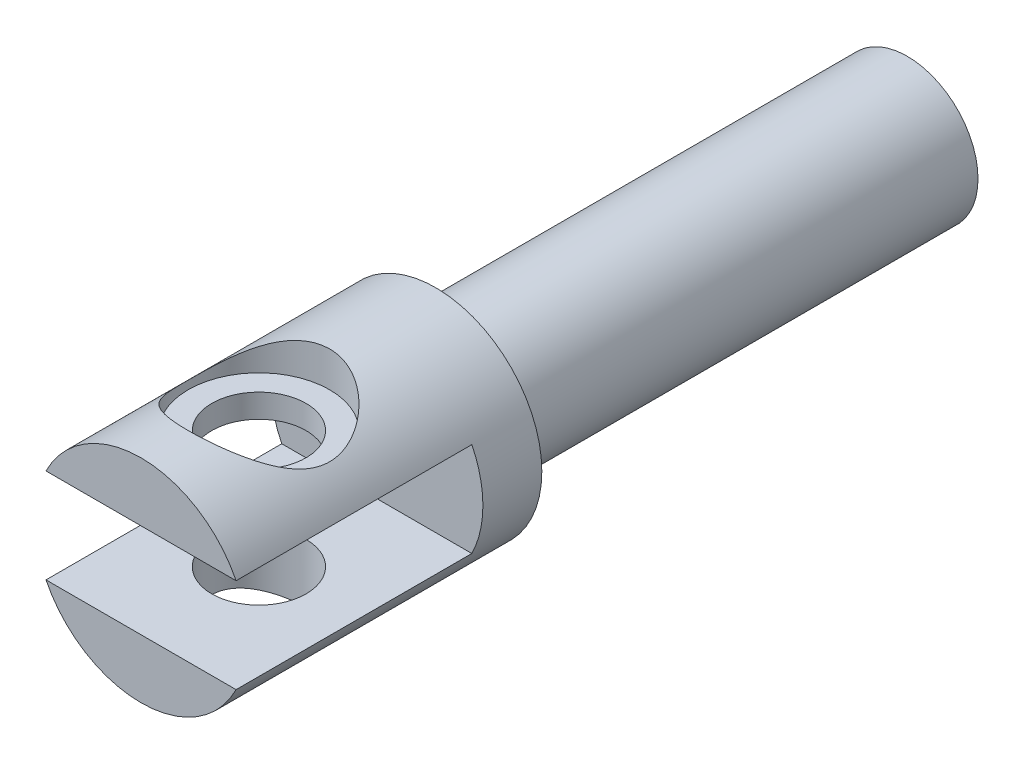
SolidWorks part; units mm, degrees
material "1.0545 (S355N)"
ref_plane "Płaszczyzna przednia" through (0, 0, 0) normal (0, 0, 1) x (1, 0, 0)
ref_plane "Płaszczyzna górna" through (0, 0, 0) normal (0, 1, 0) x (1, 0, 0)
ref_plane "Płaszczyzna prawa" through (0, 0, 0) normal (1, 0, 0) x (0, 0, -1)
sketch "Szkic1" plane through (0, 0, 0) normal (0, 1, 0) x (1, 0, 0)
  line L0 (0, -44.41) -> (0, 49.6533) construction
  line L1 (-9, 0) -> (9, 0)
  line L2 (-9, 0) -> (-9, -25)
  line L3 (-9, -25) -> (9, -25)
  line L4 (9, 0) -> (9, -25)
  line L5 (-6, 40) -> (6, 40)
  line L6 (-6, 40) -> (-6, 0)
  line L7 (-6, 0) -> (6, 0)
  line L8 (6, 40) -> (6, 0)
  point P8 (0, 0)
  point P9 (0, 0)
  dimension "D1" = 12
  dimension "D2" = 18
  dimension "D3" = 40
  dimension "D4" = 25
revolve "Obrót1" add sketch "Szkic1" angle 360 about L0 region at (4.5, 0, 12.5) region at (3, 0, -20)
sketch "Szkic2" plane through (0, 0, 25) normal (0, 0, 1) x (1, 0, 0)
  line L1 (-9, 4) -> (9, 4)
  line L2 (-9, 4) -> (-9, -4)
  line L3 (-9, -4) -> (9, -4)
  line L4 (9, 4) -> (9, -4)
  circle A2 centre (0, 0) radius 9 construction
  point P4 (0, 4)
  point P6 (-9, 0)
  point P7 (9, 0)
  dimension "D1" = 8
extrude "Wytnij-wyciągnięcie1" cut sketch "Szkic2" against normal blind 20
sketch "Szkic3" plane through (0, 0, 0) normal (0, 1, 0) x (1, 0, 0)
  line L0 (-8.0623, -5) -> (8.0623, -5) construction
  circle A0 centre (0, -15) radius 4
  circle A1 centre (0, -15) radius 6
  dimension "D2" = 8
  dimension "D3" = 12
  dimension "D1" = 10
extrude "Wytnij-wyciągnięcie2" cut sketch "Szkic3" against normal through all both and the other way through all contours A0
extrude "Wytnij-wyciągnięcie3" cut sketch "Szkic3<4>" along normal through all from offset 6
sketch "Szkic3<4>" plane through (0, 0, 0) normal (0, 1, 0) x (1, 0, 0) same geometry as "Szkic3"
equation "\"D1@Wytnij-wyciągnięcie1\"=\"D4@Szkic1\" - 5"
